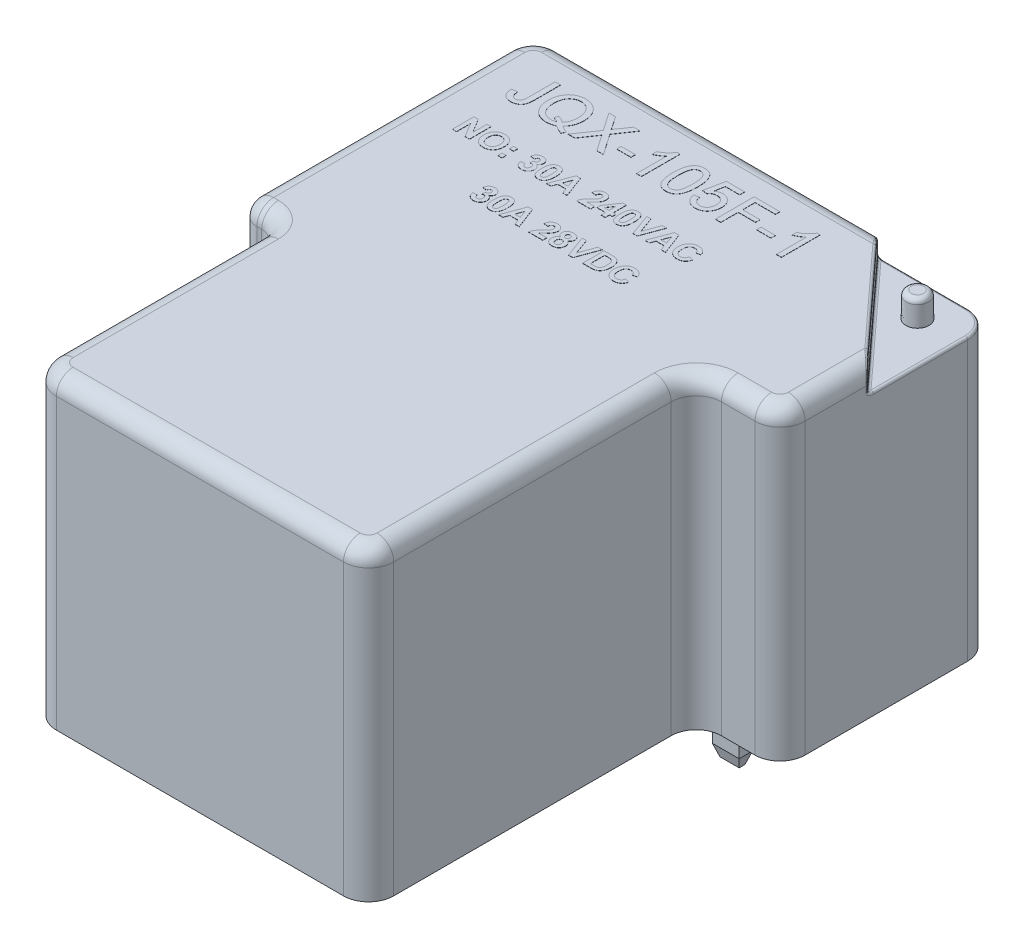
SolidWorks part; units mm, degrees
material "ABS"
ref_plane "Plan de face" through (0, 0, 0) normal (0, 0, 1) x (1, 0, 0)
ref_plane "Plan de dessus" through (0, 0, 0) normal (0, 1, 0) x (1, 0, 0)
ref_plane "Plan de droite" through (0, 0, 0) normal (1, 0, 0) x (0, 0, -1)
sketch "Sketch1" plane through (0, 0, 0) normal (0, 1, 0) x (1, 0, 0)
  line L0 (6.3474, 3.43) -> (15.7691, 3.43) construction
  line L1 (-12.215, 16.13) -> (12.215, 16.13)
  line L2 (-13.715, 14.63) -> (-13.715, -0.37)
  line L3 (-9.925, -16.13) -> (7.215, -16.13)
  line L4 (13.715, 14.63) -> (13.715, 4.93)
  line L5 (-13.715, 16.13) -> (13.715, -16.13) construction
  line L6 (-13.715, -16.13) -> (13.715, 16.13) construction
  line L7 (-15.2349, -1.37) -> (-9.5336, -1.37) construction
  line L8 (-11.425, 0.5684) -> (-11.425, -18.8093) construction
  line L9 (8.715, 5.425) -> (8.715, -18.1779) construction
  line L10 (8.715, -14.63) -> (8.715, 1.93)
  line L11 (10.215, 3.43) -> (12.215, 3.43)
  line L12 (-11.425, -14.63) -> (-11.425, -2.37)
  line L13 (-12.425, -1.37) -> (-12.715, -1.37)
  arc A0 (-12.215, 16.13) -> (-13.715, 14.63) centre (-12.215, 14.63) ccw
  arc A1 (12.215, 16.13) -> (13.715, 14.63) centre (12.215, 14.63) cw
  arc A2 (8.715, -14.63) -> (7.215, -16.13) centre (7.215, -14.63) cw
  arc A3 (-11.425, -14.63) -> (-9.925, -16.13) centre (-9.925, -14.63) ccw
  arc A4 (8.715, 1.93) -> (10.215, 3.43) centre (10.215, 1.93) cw
  arc A5 (12.215, 3.43) -> (13.715, 4.93) centre (12.215, 4.93) ccw
  arc A6 (-11.425, -2.37) -> (-12.425, -1.37) centre (-12.425, -2.37) ccw
  arc A7 (-12.715, -1.37) -> (-13.715, -0.37) centre (-12.715, -0.37) cw
  point P0 (0, 0)
  point P9 (11.0582, 3.43)
  point P12 (-12.3842, -1.37)
  point P15 (-11.425, -9.1204)
  point P18 (8.715, -6.3765)
  point P32 (8.715, -16.13)
  point P35 (-11.425, -16.13)
  point P38 (8.715, 3.43)
  point P41 (13.715, 3.43)
  point P44 (-11.425, -1.37)
  point P47 (-13.715, -1.37)
  dimension "D7" = 1.5
  dimension "D8" = 1
  dimension "D1" = 27.43
  dimension "D2" = 32.26
  dimension "D3" = 2.29
  dimension "D4" = 5
  dimension "D5" = 12.7
  dimension "D6" = 17.5
extrude "Boss-Extrude1" add sketch "Sketch1" along normal blind 18.26
fillet "Fillet1" radius 1 16 edges at (-10.9857, 18.26, 15.6907) (-11.425, 18.26, 8.5) (-11.7179, 18.26, 1.6629) (-12.57, 18.26, 1.37) (-13.4221, 18.26, 1.0771) (-13.715, 18.26, -7.13) (-13.2757, 18.26, -15.6907) (0, 18.26, -16.13) (13.2757, 18.26, -15.6907) (13.715, 18.26, -9.78) (13.2757, 18.26, -3.8693) (11.215, 18.26, -3.43) (9.1543, 18.26, -2.9907) (8.715, 18.26, 6.35) (8.2757, 18.26, 15.6907) (-1.355, 18.26, 16.13)
sketch "Sketch2" plane through (0, 0, 0) normal (0, -1, 0) x (1, 0, 0)
  line L16 (-12.215, -15.53) -> (12.215, -15.53)
  line L17 (13.115, -14.63) -> (13.115, -4.93)
  line L18 (12.215, -4.03) -> (10.215, -4.03)
  line L19 (8.115, -1.93) -> (8.115, 14.63)
  line L20 (7.215, 15.53) -> (-9.925, 15.53)
  line L21 (-10.825, 14.63) -> (-10.825, 2.37)
  line L22 (-12.425, 0.77) -> (-12.715, 0.77)
  line L23 (-13.115, 0.37) -> (-13.115, -14.63)
  line L24 (-12.215, -15.53) -> (12.215, -15.53)
  line L25 (13.115, -14.63) -> (13.115, -4.93)
  line L26 (12.215, -4.03) -> (10.215, -4.03)
  line L27 (8.115, -1.93) -> (8.115, 14.63)
  line L28 (7.215, 15.53) -> (-9.925, 15.53)
  line L29 (-10.825, 14.63) -> (-10.825, 2.37)
  line L30 (-12.425, 0.77) -> (-12.715, 0.77)
  line L31 (-13.115, 0.37) -> (-13.115, -14.63)
  arc A16 (-13.115, -14.63) -> (-12.215, -15.53) centre (-12.215, -14.63) ccw
  arc A17 (12.215, -15.53) -> (13.115, -14.63) centre (12.215, -14.63) ccw
  arc A18 (13.115, -4.93) -> (12.215, -4.03) centre (12.215, -4.93) ccw
  arc A19 (8.115, -1.93) -> (10.215, -4.03) centre (10.215, -1.93) ccw
  arc A20 (8.115, 14.63) -> (7.215, 15.53) centre (7.215, 14.63) ccw
  arc A21 (-9.925, 15.53) -> (-10.825, 14.63) centre (-9.925, 14.63) ccw
  arc A22 (-12.425, 0.77) -> (-10.825, 2.37) centre (-12.425, 2.37) ccw
  arc A23 (-12.715, 0.77) -> (-13.115, 0.37) centre (-12.715, 0.37) ccw
  arc A24 (-13.115, -14.63) -> (-12.215, -15.53) centre (-12.215, -14.63) ccw
  arc A25 (12.215, -15.53) -> (13.115, -14.63) centre (12.215, -14.63) ccw
  arc A26 (13.115, -4.93) -> (12.215, -4.03) centre (12.215, -4.93) ccw
  arc A27 (8.115, -1.93) -> (10.215, -4.03) centre (10.215, -1.93) ccw
  arc A28 (8.115, 14.63) -> (7.215, 15.53) centre (7.215, 14.63) ccw
  arc A29 (-9.925, 15.53) -> (-10.825, 14.63) centre (-9.925, 14.63) ccw
  arc A30 (-12.425, 0.77) -> (-10.825, 2.37) centre (-12.425, 2.37) ccw
  arc A31 (-12.715, 0.77) -> (-13.115, 0.37) centre (-12.715, 0.37) ccw
  dimension "D1" = 0.6
extrude "Cut-Extrude1" cut sketch "Sketch2" against normal blind 0.2
sketch "Sketch3" plane through (0, 0.2, 0) normal (0, -1, 0) x (1, 0, 0)
  line L0 (13.715, -4.93) -> (13.715, -14.63) construction
  line L7 (12.215, -16.13) -> (-12.215, -16.13) construction
  line L9 (7.535, -5.57) -> (9.135, -5.57)
  line L10 (7.535, -5.57) -> (7.535, -6.37)
  line L11 (7.535, -6.37) -> (9.135, -6.37)
  line L12 (9.135, -5.57) -> (9.135, -6.37)
  line L13 (7.535, -5.57) -> (9.135, -6.37) construction
  line L14 (7.535, -6.37) -> (9.135, -5.57) construction
  line L15 (-10.015, -2.86) -> (-8.875, -2.86)
  line L16 (-10.015, -2.86) -> (-10.015, -4)
  line L17 (-10.015, -4) -> (-8.875, -4)
  line L18 (-8.875, -2.86) -> (-8.875, -4)
  line L19 (-10.015, -2.86) -> (-8.875, -4) construction
  line L20 (-10.015, -4) -> (-8.875, -2.86) construction
  line L22 (-1.125, 12.38) -> (0.015, 12.38)
  line L23 (-1.125, 12.38) -> (-1.125, 11.24)
  line L24 (-1.125, 11.24) -> (0.015, 11.24)
  line L25 (0.015, 12.38) -> (0.015, 11.24)
  line L26 (-1.125, 12.38) -> (0.015, 11.24) construction
  line L27 (-1.125, 11.24) -> (0.015, 12.38) construction
  line L28 (-5.955, 9.59) -> (-5.315, 9.59)
  line L29 (-5.955, 9.59) -> (-5.955, 8.95)
  line L30 (-5.955, 8.95) -> (-5.315, 8.95)
  line L31 (-5.315, 9.59) -> (-5.315, 8.95)
  line L32 (-5.955, 9.59) -> (-5.315, 8.95) construction
  line L33 (-5.955, 8.95) -> (-5.315, 9.59) construction
  line L34 (4.205, 9.59) -> (4.845, 9.59)
  line L35 (4.205, 9.59) -> (4.205, 8.95)
  line L36 (4.205, 8.95) -> (4.845, 8.95)
  line L37 (4.845, 9.59) -> (4.845, 8.95)
  line L38 (4.205, 9.59) -> (4.845, 8.95) construction
  line L39 (4.205, 8.95) -> (4.845, 9.59) construction
  point P0 (8.335, -13.59)
  point P9 (8.335, -5.97)
  point P14 (-9.445, -3.43)
  point P19 (-0.555, 11.81)
  point P24 (-5.635, 9.27)
  point P29 (4.525, 9.27)
  dimension "D1" = 5.38
  dimension "D2" = 2.54
  dimension "D5" = 7.62
  dimension "D6" = 1.6
  dimension "D7" = 0.8
  dimension "D8" = 1.14
  dimension "D9" = 2.54
  dimension "D10" = 17.78
  dimension "D11" = 1.14
  dimension "D12" = 8.89
  dimension "D13" = 15.24
  dimension "D14" = 0.64
  dimension "D15" = 3.81
  dimension "D16" = 15.24
  dimension "D17" = 15.24
  dimension "D18" = 13.97
extrude "Boss-Extrude2" add sketch "Sketch3" along normal blind 3.7
chamfer "Chamfer1" distance 0.7 angle 18 12 edges at (8.335, -3.5, -6.37) (7.535, -3.5, -5.97) (9.135, -3.5, -5.97) (8.335, -3.5, -5.57) (0.015, -3.5, 11.81) (-0.555, -3.5, 11.24) (-1.125, -3.5, 11.81) (-0.555, -3.5, 12.38) (-8.875, -3.5, -3.43) (-9.445, -3.5, -4) (-10.015, -3.5, -3.43) (-9.445, -3.5, -2.86) first distance on face at (8.335, -1.65, -6.37) first distance on face at (7.535, -1.65, -5.97) first distance on face at (9.135, -1.65, -5.97) first distance on face at (8.335, -1.65, -5.57) first distance on face at (0.015, -1.65, 11.81) first distance on face at (-0.555, -1.65, 11.24) first distance on face at (-1.125, -1.65, 11.81) first distance on face at (-0.555, -1.65, 12.38) first distance on face at (-8.875, -1.65, -3.43) first distance on face at (-9.445, -1.65, -4) first distance on face at (-10.015, -1.65, -3.43) first distance on face at (-9.445, -1.65, -2.86)
sketch "Sketch4" plane through (0, 18.26, 0) normal (0, 1, 0) x (1, 0, 0)
  line L0 (-11.0308, 11.3325) -> (2.2127, 11.3325) construction
  line L1 (-11.0308, 8.4877) -> (4.9474, 8.4877) construction
  text T0 "JQX-105F-1" font "Arial" height in points 9
  text T1 "NO: 30A 240VAC\r\n        30A 28VDC" font "Arial" height in points 5
extrude "Boss-Extrude3" add sketch "Sketch4" along normal blind 0.01
sketch "Sketch5" plane through (0, 18.26, 0) normal (0, 1, 0) x (1, 0, 0)
  line L0 (3.9465, 19.2989) -> (16.2191, 5.8884)
  line L3 (16.2191, 5.8884) -> (16.2191, 19.2989)
  line L4 (16.2191, 19.2989) -> (3.9465, 19.2989)
extrude "Cut-Extrude2" cut sketch "Sketch5" against normal blind 1.5
sketch "Sketch6" plane through (0, 16.76, 0) normal (0, 1, 0) x (1, 0, 0)
  circle A0 centre (11.2748, 14.0755) radius 0.6916
extrude "Boss-Extrude4" add sketch "Sketch6" along normal blind 1.5 draft 1
fillet "Fillet3" radius 0.3 1 edges at (11.2748, 18.26, -13.4101)
fillet "Fillet4" radius 0.15 9 edges at (13.2757, 16.76, -15.6907) (9.5307, 16.76, -16.13) (13.715, 16.76, -11.6273) (6.8465, 17.01, -16.13) (10.2807, 16.76, -12.3773) (13.715, 17.01, -8.6247) (13.4221, 17.9671, -8.9447) (10.2383, 18.26, -12.4237) (7.1145, 17.9671, -15.8371)
